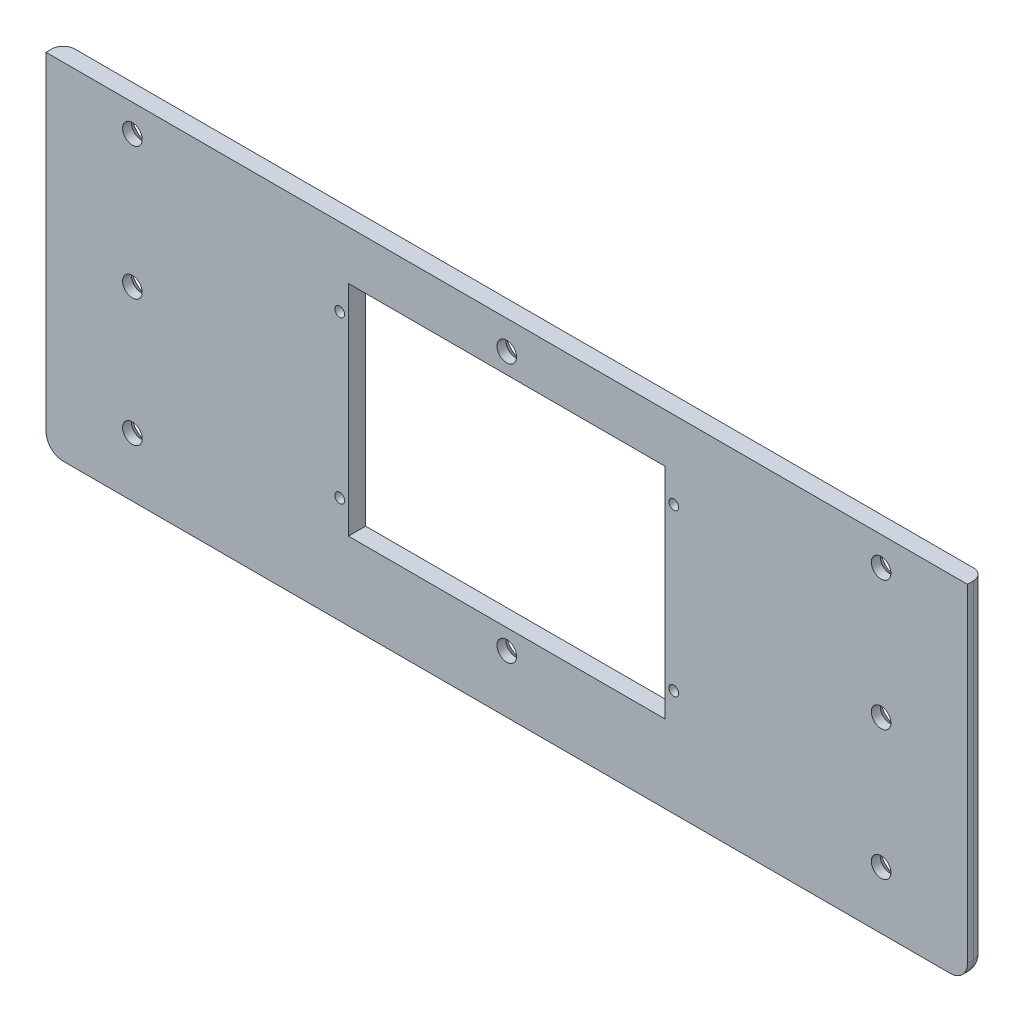
SolidWorks part; units mm, degrees
ref_plane "Front Plane" through (0, 0, 0) normal (0, 0, 1) x (1, 0, 0)
ref_plane "Top Plane" through (0, 0, 0) normal (0, 1, 0) x (1, 0, 0)
ref_plane "Right Plane" through (0, 0, 0) normal (1, 0, 0) x (0, 0, -1)
sketch "Sketch1" plane through (0, 0, 0) normal (0, 0, 1) x (1, 0, 0)
  line L1 (0, 0) -> (160, 0)
  line L2 (0, 0) -> (0, 60)
  line L3 (0, 60) -> (160, 60)
  line L4 (160, 0) -> (160, 60)
  dimension "D1" = 160
  dimension "D2" = 60
extrude "Boss-Extrude1" add sketch "Sketch1" along normal blind 3
sketch "Sketch2" plane through (0, 0, 0) normal (0, 0, -1) x (-1, 0, 0)
  line L0 (-53.5, 14.5) -> (-53.5, 50.5) construction
  line L1 (-106.5, 14.5) -> (-53.5, 14.5) construction
  line L2 (-106.5, 50.5) -> (-106.5, 14.5) construction
  line L3 (-53.5, 50.5) -> (-106.5, 50.5) construction
  line L4 (-53.5, 14.5) -> (-53.5, 50.5) construction
  line L5 (-106.5, 14.5) -> (-53.5, 14.5) construction
  line L6 (-106.5, 50.5) -> (-106.5, 14.5) construction
  line L7 (-53.5, 50.5) -> (-106.5, 50.5) construction
  line L9 (-107.5, 51.5) -> (-52.5, 51.5)
  line L10 (-107.5, 51.5) -> (-107.5, 13.5)
  line L11 (-107.5, 13.5) -> (-52.5, 13.5)
  line L12 (-52.5, 51.5) -> (-52.5, 13.5)
  circle A0 centre (-51, 18.5) radius 1.15 construction
  circle A1 centre (-51, 46.5) radius 1.15 construction
  circle A2 centre (-109, 18.5) radius 1.15 construction
  circle A3 centre (-109, 46.5) radius 1.15 construction
  circle A4 centre (-51, 18.5) radius 1.15 construction
  circle A5 centre (-51, 46.5) radius 1.15 construction
  circle A6 centre (-109, 18.5) radius 1.15 construction
  circle A7 centre (-109, 46.5) radius 1.15 construction
  circle A8 centre (-109, 46.5) radius 0.85
  circle A9 centre (-109, 18.5) radius 0.85
  circle A10 centre (-51, 18.5) radius 0.85
  circle A11 centre (-51, 46.5) radius 0.85
  dimension "D5" = 1.7
  dimension "D1" = 1
  dimension "D2" = 1
  dimension "D3" = 1
  dimension "D4" = 1
extrude "Cut-Extrude1" cut sketch "Sketch2" against normal through all
fillet "Fillet1" radius 2 3 edges at (80, 0, 0) (0, 30, 0) (160, 30, 0)
fillet "Fillet2" radius 3 4 edges at (159.4142, 0.5858, 0.5858) (0.5858, 0.5858, 0.5858) (0, 0, 2.5) (160, 0, 2.5)
sketch "Sketch4" plane through (0, 0, 0) normal (0, 0, -1) x (-1, 0, 0)
  line L0 (-80, 60) -> (-80, 55) construction
  line L1 (-158, 60) -> (-2, 60) construction
  line L2 (-80, 55) -> (-145, 55) construction
  line L3 (-145, 10) -> (-80, 10) construction
  line L4 (-80, 10) -> (-80, 55) construction
  circle A0 centre (-15, 55.2387) radius 3 construction
  circle A1 centre (-15, 32.2613) radius 3 construction
  circle A2 centre (-15, 10.2387) radius 3 construction
  circle A3 centre (-145, 10) radius 3 construction
  circle A4 centre (-145, 32.5) radius 3 construction
  circle A5 centre (-145, 55) radius 3 construction
  circle A6 centre (-15, 55.2387) radius 3
  circle A7 centre (-15, 32.2613) radius 3
  circle A8 centre (-15, 10.2387) radius 3
  circle A9 centre (-145, 10) radius 3
  circle A10 centre (-145, 32.5) radius 3
  circle A11 centre (-145, 55) radius 3
  circle A12 centre (-80, 55) radius 3
  circle A13 centre (-80, 10) radius 3
hole_wizard "CSK for M3 Flat Head Machine Screw1" positions "3DSketch1" profile "Sketch5" countersink size "M3" standard "ANSI Metric" end condition through all
sketch3d "3DSketch1"
  point P0 (145, 55, 0)
  point P3 (145, 32.5, 0)
  point P6 (145, 10, 0)
  point P9 (80, 10, 0)
  point P12 (80, 55, 0)
  point P15 (15, 55.2387, 0)
  point P18 (15, 32.2613, 0)
  point P21 (15, 10.2387, 0)
sketch "Sketch5" plane through (145, 55, 0) normal (1, 0, 0) x (0, 1, 0)
  line L0 (0, 0) -> (0, 3)
  line L1 (0, 3) -> (1.7, 3)
  line L2 (1.7, 3) -> (1.7, 1.45)
  line L3 (1.7, 1.45) -> (3.15, 0)
  line L5 (3.15, 0) -> (0, 0)
  line L6 (-1.7, 1.45) -> (-3.15, 0) construction
  line L11 (0, -6.35) -> (0, 107.95) construction
  dimension "Thru Hole Dia." = 3.4
  dimension "Thru Hole Depth" = 3
  dimension "Near C'Sink Dia." = 6.3
  dimension "Near C'Sink Angle" = 90
